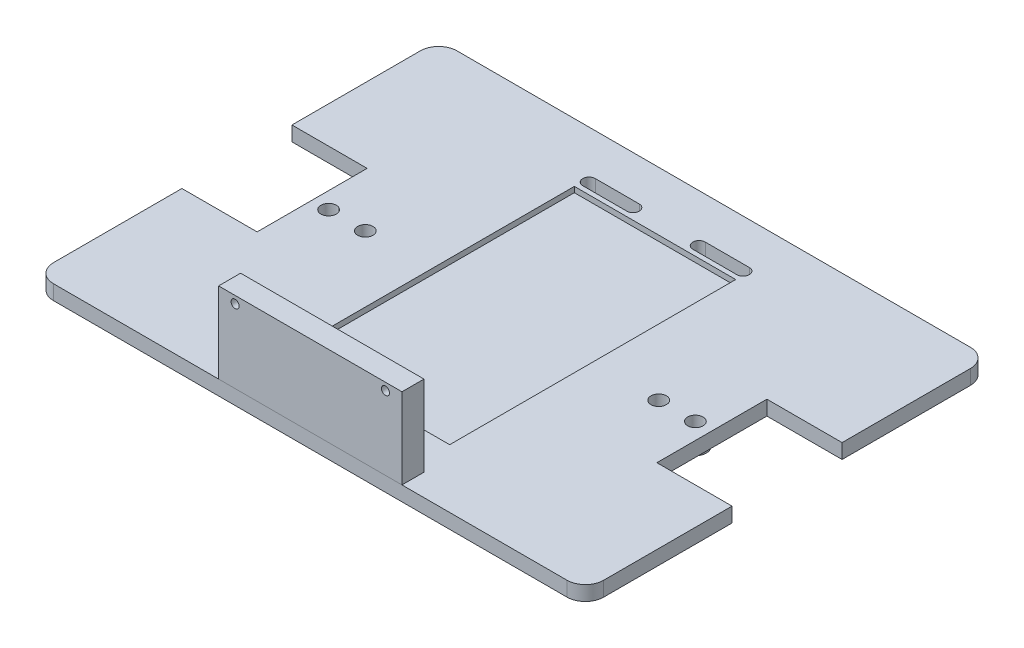
SolidWorks part; units mm, degrees
ref_plane "Front Plane" through (0, 0, 0) normal (0, 0, 1) x (1, 0, 0)
ref_plane "Top Plane" through (0, 0, 0) normal (0, 1, 0) x (1, 0, 0)
ref_plane "Right Plane" through (0, 0, 0) normal (1, 0, 0) x (0, 0, -1)
sketch "Sketch1" plane through (0, 0, 0) normal (0, 1, 0) x (1, 0, 0)
  line L0 (-75, 0) -> (75, 0) construction
  line L1 (-75, -55) -> (75, -55)
  line L2 (-75, -55) -> (-75, 55)
  line L3 (-75, 55) -> (75, 55)
  line L4 (75, -55) -> (75, 55)
  line L5 (-75, -55) -> (75, 55) construction
  line L6 (-75, 55) -> (75, -55) construction
  point P0 (0, 0)
  dimension "D1" = 150
  dimension "D2" = 110
extrude "Boss-Extrude1" add sketch "Sketch1" along normal blind 4
fillet "Fillet1" radius 5 4 edges at (-75, 2, -55) (-75, 2, 55) (75, 2, -55) (75, 2, 55)
sketch "Sketch2" plane through (0, 4, 0) normal (0, 1, 0) x (1, 0, 0)
  line L0 (-75, 0) -> (75, 0) construction
  line L1 (-75, 50) -> (-75, -50) construction
  line L2 (75, -50) -> (75, 50) construction
  line L3 (0, 55) -> (0, -55) construction
  line L4 (70, 55) -> (-70, 55) construction
  line L5 (-70, -55) -> (70, -55) construction
  circle A0 centre (-50, 0) radius 2.1
  circle A1 centre (-40, 0) radius 2.1
  dimension "D1" = 4.2
  dimension "D2" = 50
  dimension "D3" = 4.2
  dimension "D4" = 40
extrude "Cut-Extrude1" cut sketch "Sketch2" against normal through all
sketch "Sketch3" plane through (0, 0, 0) normal (0, -1, 0) x (1, 0, 0)
  line L0 (-75, 0) -> (75, 0) construction
  line L1 (-75, -50) -> (-75, 50) construction
  line L2 (75, 50) -> (75, -50) construction
  line L3 (0, 55) -> (0, -55) construction
  line L4 (-70, 55) -> (70, 55) construction
  line L5 (70, -55) -> (-70, -55) construction
  circle A0 centre (-50, 0) radius 3
  circle A1 centre (-40, 0) radius 3
  dimension "D1" = 6
  dimension "D2" = 6
extrude "Boss-Extrude2" add sketch "Sketch3" along normal blind 2
mirror "Mirror1" about plane through (0, 0, 0) normal (1, 0, 0) of "Boss-Extrude2", "Cut-Extrude1"
sketch "Sketch4" plane through (0, 4, 0) normal (0, 1, 0) x (1, 0, 0)
  line L0 (0, -55) -> (0, 55) construction
  line L1 (-22, -39) -> (-6, -39)
  line L2 (-22, -39) -> (-22, 39)
  line L3 (-22, 39) -> (22, 39)
  line L4 (22, -39) -> (22, 39)
  line L5 (-22, -39) -> (22, 39) construction
  line L6 (-22, 39) -> (22, -39) construction
  line L7 (-70, -55) -> (70, -55) construction
  line L8 (70, 55) -> (-70, 55) construction
  line L9 (6, -39) -> (22, -39)
  line L10 (-6, -43) -> (6, -43)
  line L11 (-6, -43) -> (-6, -39)
  line L13 (6, -43) -> (6, -39)
  line L14 (-6, -43) -> (6, -39) construction
  line L15 (-6, -39) -> (6, -43) construction
  point P0 (0, 0)
  point P15 (0, -41)
  dimension "D1" = 44
  dimension "D2" = 78
  dimension "D3" = 0
  dimension "D4" = 4
  dimension "D5" = 12
extrude "Cut-Extrude2" cut sketch "Sketch4" against normal blind 1.5
sketch "Sketch7" plane through (0, 0, 55) normal (0, 0, 1) x (1, 0, 0)
  line L0 (-70, 4) -> (70, 4) construction
  line L1 (-25, 4) -> (25, 4)
  line L2 (-25, 4) -> (-25, 26)
  line L3 (-25, 26) -> (25, 26)
  line L4 (25, 4) -> (25, 26)
  line L5 (-25, 4) -> (25, 26) construction
  line L6 (-25, 26) -> (25, 4) construction
  line L7 (70, 0) -> (70, 4) construction
  point P0 (0, 4)
  point P10 (0, 26)
  dimension "D1" = 50
  dimension "D2" = 22
  dimension "D3" = 45
extrude "Boss-Extrude4" add sketch "Sketch7" against normal blind 6 separate body
sketch "Sketch8" plane through (0, 0, 49) normal (0, 0, -1) x (-1, 0, 0)
  line L0 (0, 4) -> (0, 26) construction
  line L1 (25, 4) -> (-25, 4) construction
  line L2 (-25, 26) -> (25, 26) construction
  circle A0 centre (-20.5, 24) radius 1.1
  circle A1 centre (20.5, 24) radius 1.1
  dimension "D1" = 2.2
  dimension "D2" = 20.5
  dimension "D3" = 20
extrude "Cut-Extrude3" cut sketch "Sketch8" against normal through all
sketch "Sketch9" plane through (0, 0, 0) normal (0, -1, 0) x (1, 0, 0)
  line L0 (0, 55) -> (0, -55) construction
  line L1 (-70, 55) -> (70, 55) construction
  line L2 (70, -55) -> (-70, -55) construction
  line L3 (-21, -42) -> (-9, -42) construction
  line L4 (-21, -40.3) -> (-9, -40.3)
  line L5 (-21, -43.7) -> (-9, -43.7)
  line L6 (-75, 0) -> (75, 0) construction
  line L7 (-75, -50) -> (-75, 50) construction
  line L8 (75, 50) -> (75, -50) construction
  line L9 (21, -42) -> (9, -42) construction
  line L10 (21, -40.3) -> (9, -40.3)
  line L11 (21, -43.7) -> (9, -43.7)
  arc A0 (-21, -40.3) -> (-21, -43.7) centre (-21, -42) ccw
  arc A1 (-9, -43.7) -> (-9, -40.3) centre (-9, -42) ccw
  arc A2 (21, -40.3) -> (21, -43.7) centre (21, -42) cw
  arc A3 (9, -43.7) -> (9, -40.3) centre (9, -42) cw
  point P8 (-15, -42)
  point P22 (15, -42)
  dimension "D1" = 12
  dimension "D2" = 3.4
  dimension "D3" = 15
  dimension "D4" = 42
extrude "Cut-Extrude4" cut sketch "Sketch9" against normal through all
sketch "Sketch10" plane through (0, 4, 0) normal (0, 1, 0) x (1, 0, 0)
  circle A0 centre (-50, 0) radius 2.1
  circle A1 centre (-40, 0) radius 2.1
  circle A2 centre (40, 0) radius 2.1
  circle A3 centre (50, 0) radius 2.1
  dimension "D1" = 4.2
  dimension "D2" = 4.2
  dimension "D3" = 4.2
  dimension "D4" = 4.2
extrude "Cut-Extrude5" cut sketch "Sketch10" against normal through all
sketch "Sketch11" plane through (0, 4, 0) normal (0, 1, 0) x (1, 0, 0)
  line L0 (75, -50) -> (75, 50) construction
  line L1 (54.5, -15) -> (75, -15)
  line L2 (54.5, -15) -> (54.5, 15)
  line L3 (54.5, 15) -> (75, 15)
  line L4 (75, -15) -> (75, 15)
  line L5 (54.5, -15) -> (75, 15) construction
  line L6 (54.5, 15) -> (75, -15) construction
  line L7 (0, -15.4) -> (0, 15.4) construction
  line L8 (-54.5, 15) -> (-75, -15) construction
  line L9 (-54.5, -15) -> (-75, 15) construction
  line L10 (-75, -15) -> (-75, 15)
  line L11 (-54.5, 15) -> (-75, 15)
  line L12 (-54.5, -15) -> (-54.5, 15)
  line L13 (-54.5, -15) -> (-75, -15)
  point P0 (64.75, 0)
  point P14 (-64.75, 0)
  dimension "D1" = 54.5
  dimension "D2" = 15
  dimension "D3" = 15
extrude "Cut-Extrude6" cut sketch "Sketch11" against normal through all
